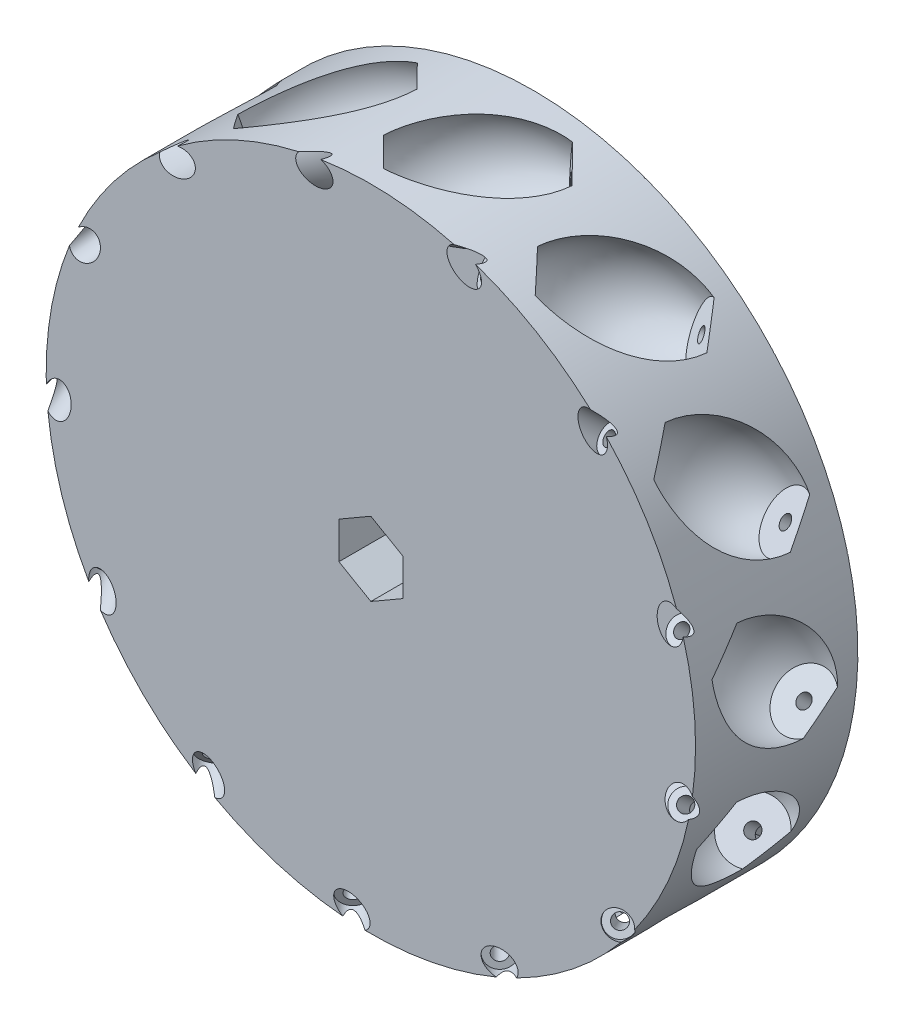
SolidWorks part; units mm, degrees
ref_plane "Front Plane" through (0, 0, 0) normal (0, 0, 1) x (1, 0, 0)
ref_plane "Top Plane" through (0, 0, 0) normal (0, 1, 0) x (1, 0, 0)
ref_plane "Right Plane" through (0, 0, 0) normal (1, 0, 0) x (0, 0, -1)
sketch "Sketch1" plane through (0, 0, 0) normal (0, 0, 1) x (1, 0, 0)
  line L1 (0, 8.6603) -> (-7.5, 4.3301)
  line L2 (-7.5, 4.3301) -> (-7.5, -4.3301)
  line L3 (-7.5, -4.3301) -> (0, -8.6603)
  line L4 (0, -8.6603) -> (7.5, -4.3301)
  line L5 (7.5, -4.3301) -> (7.5, 4.3301)
  line L6 (7.5, 4.3301) -> (0, 8.6603)
  circle A0 centre (0, 0) radius 76.2
  circle A1 centre (0, 0) radius 7.5 construction
  dimension "D1" = 152.4
  dimension "D2" = 15
extrude "Boss-Extrude1" add sketch "Sketch1" along normal blind 38.1
ref_plane "Plane1" through (65.9911, 38.1, 0) normal (0.866, 0.5, 0) x (0, 0, -1)
ref_plane "Plane2" through (61.5917, 35.56, 0) normal (0.866, 0.5, 0) x (0, 0, -1)
sketch "Sketch2" plane through (61.5917, 35.56, 0) normal (0.866, 0.5, 0) x (0, 0, -1)
  line L0 (0, -19.05) -> (-38.1, 19.05) construction
  line L1 (-38.1, 76.2) -> (-38.1, -76.2) construction
  line L2 (-38.1, 19.05) -> (0, 19.05) construction
  line L3 (0, -76.2) -> (0, 76.2) construction
  line L5 (-13.6618, -12.5724) -> (-6.4776, -5.3882) construction
  line L7 (-31.6224, 5.3882) -> (-24.4382, 12.5724) construction
  line L9 (-13.6618, -12.5724) -> (-24.4382, 12.5724) construction
  line L10 (-31.6224, 5.3882) -> (-6.4776, -5.3882) construction
  line L14 (-30.1516, 11.1016) -> (-7.9484, -11.1016)
  line L15 (-34.8334, 6.4198) -> (-25.4698, 15.7834)
  line L16 (-12.6302, -15.7834) -> (-3.2666, -6.4198)
  arc A0 (-24.4382, 12.5724) -> (-6.4776, -5.3882) centre (-28.8983, -9.8483) cw construction
  arc A1 (-31.6224, 5.3882) -> (-13.6618, -12.5724) centre (-9.2017, 9.8483) ccw construction
  arc A2 (-25.4698, 15.7834) -> (-3.2666, -6.4198) centre (-28.8983, -9.8483) cw
  arc A3 (-34.8334, 6.4198) -> (-12.6302, -15.7834) centre (-9.2017, 9.8483) ccw
  point P5 (-29.4584, 10.4084)
  point P9 (0, 0)
  point P10 (-19.05, 0)
  point P11 (-19.05, 0)
  point P16 (0, 0)
  point P17 (-16.5492, -14.4512)
  point P22 (-10.0697, -8.9803)
  point P29 (-8.6555, -10.3945)
  point P30 (-29.7862, 10.7362)
  point P31 (-29.4445, 10.3945)
  dimension "D5" = 22.86
  dimension "D1" = 45
  dimension "D2" = 25.4
  dimension "D3" = 10.16
  dimension "D4" = 3
revolve "Cut-Revolve1" cut sketch "Sketch2" angle 360 about L14 region at (59.7395, 38.7682, 15.3455)
sketch "Sketch4" plane through (-10.3133, 17.8631, 20.6266) normal (0.3536, -0.6124, -0.7071) x (-0.9354, -0.2315, -0.2673)
  line L0 (-77.0391, 11.8433) -> (-72.1462, 20.9192)
  line L1 (-68.3957, 14.4837) -> (-69.7298, 16.6464)
  line L2 (-69.7298, 16.6464) -> (-72.2698, 16.5724)
  line L3 (-72.2698, 16.5724) -> (-73.4757, 14.3356)
  line L4 (-73.4757, 14.3356) -> (-72.1415, 12.1729)
  line L5 (-72.1415, 12.1729) -> (-69.6015, 12.247)
  line L6 (-69.6015, 12.247) -> (-68.3957, 14.4837)
  circle A1 centre (-70.9357, 14.4097) radius 1.585
  arc A2 (-77.0391, 11.8433) -> (-72.1462, 20.9192) centre (-70.9357, 14.4097) ccw construction
  circle A3 centre (-70.9357, 14.4097) radius 3.1
  circle A4 centre (-70.9357, 14.4097) radius 2.2006 construction
  ellipse E1 centre (-11.0254, -27.0065) end of major axis (29.7052, 72.7627) minor radius 76.2 (-72.1462, 20.9192) -> (-77.0391, 11.8433) ccw construction
  point P12 (-70.9357, 14.4097)
  dimension "D1" = 3.17
  dimension "D2" = 6.2
  dimension "D3" = 5.08
extrude "Cut-Extrude1" cut sketch "Sketch4" against normal through all both and the other way through all contours A1
extrude "Cut-Extrude2" cut sketch "Sketch4<4>" along normal blind 7.62 from offset 15.24 contours A3 L6 L5 L4 L3 L2 L1 | L5 L6 L1 L2 L3 L4 A1 region at (54.2847, 43.9746, 30.3124) region at (58.8587, 45.8715, 30.9567) offset against normal yes
sketch "Sketch4<4>" plane through (-10.3133, 17.8631, 20.6266) normal (0.3536, -0.6124, -0.7071) x (-0.9354, -0.2315, -0.2673) same geometry as "Sketch4"
extrude "Cut-Extrude3" cut sketch "Sketch4<5>" against normal blind 7.62 from offset 45.72 contours L5 L6 L1 L2 L3 L4 A1 region at (54.2847, 43.9746, 30.3124)
sketch "Sketch4<5>" plane through (-10.3133, 17.8631, 20.6266) normal (0.3536, -0.6124, -0.7071) x (-0.9354, -0.2315, -0.2673) same geometry as "Sketch4"
pattern_circular "CirPattern1" count 13 over 360 about axis through (0, 0, 0) along (0, 0, 1) of "Cut-Revolve1", "Cut-Extrude1", "Cut-Extrude2", "Cut-Extrude3"
